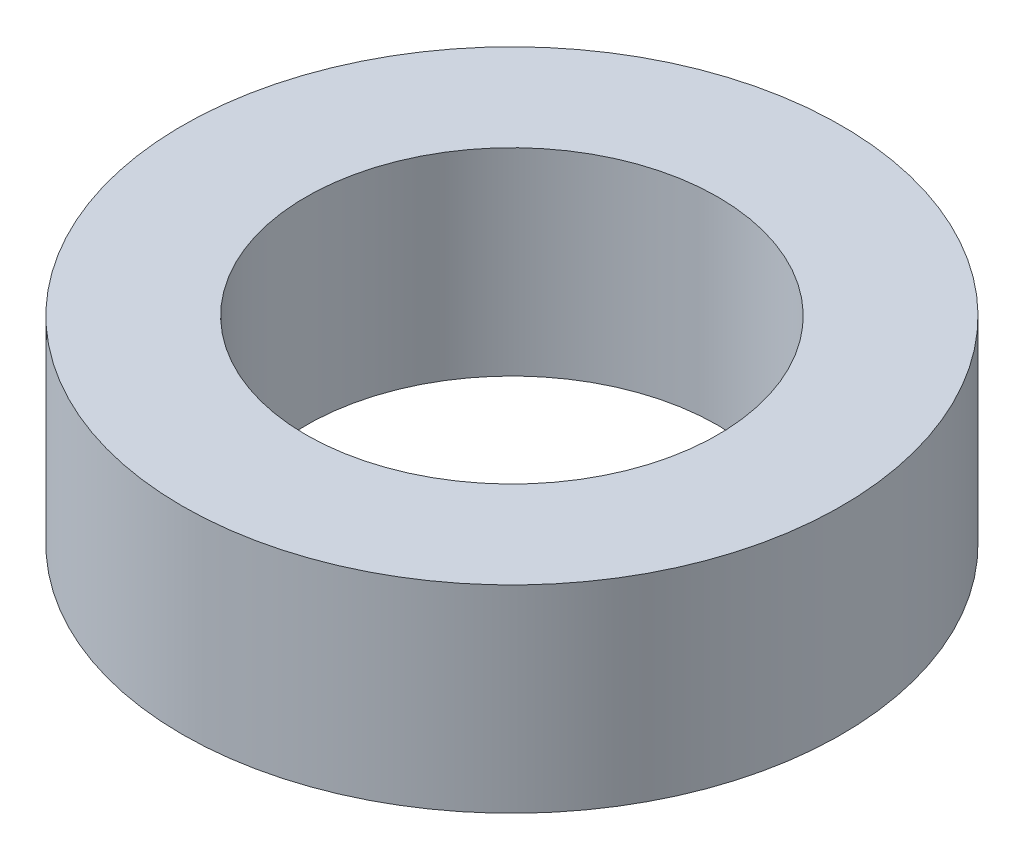
SolidWorks part; units mm, degrees
ref_plane "Front Plane" through (0, 0, 0) normal (0, 0, 1) x (1, 0, 0)
ref_plane "Top Plane" through (0, 0, 0) normal (0, 1, 0) x (1, 0, 0)
ref_plane "Right Plane" through (0, 0, 0) normal (1, 0, 0) x (0, 0, -1)
sketch "Sketch1" plane through (0, 0, 0) normal (0, 1, 0) x (1, 0, 0)
  circle A0 centre (0, 0) radius 20
  dimension "FLANGE_OD" = 40
extrude "Boss-Extrude1" add sketch "Sketch1" along normal blind 12
sketch "Sketch2" plane through (0, 0, 0) normal (0, 1, 0) x (1, 0, 0)
  circle A0 centre (0, 0) radius 12.5
  dimension "BORE_D" = 25
extrude "Cut-Extrude1" cut sketch "Sketch2" along normal through all
sketch "Sketch3" plane through (0, 12, 0) normal (0, 1, 0) x (1, 0, 0)
  circle A0 centre (0, 0) radius 8.3073 construction
  circle A1 centre (-8.3073, 0) radius 1.5
  dimension "BOLT_D" = 3
  dimension "BOLT_PCD" = 16.6145
extrude "Cut-Extrude2" cut sketch "Sketch3" against normal blind 11.2312 rebuild error yes
pattern_circular "CirPattern1" count 5 over 360 rebuild error yes
